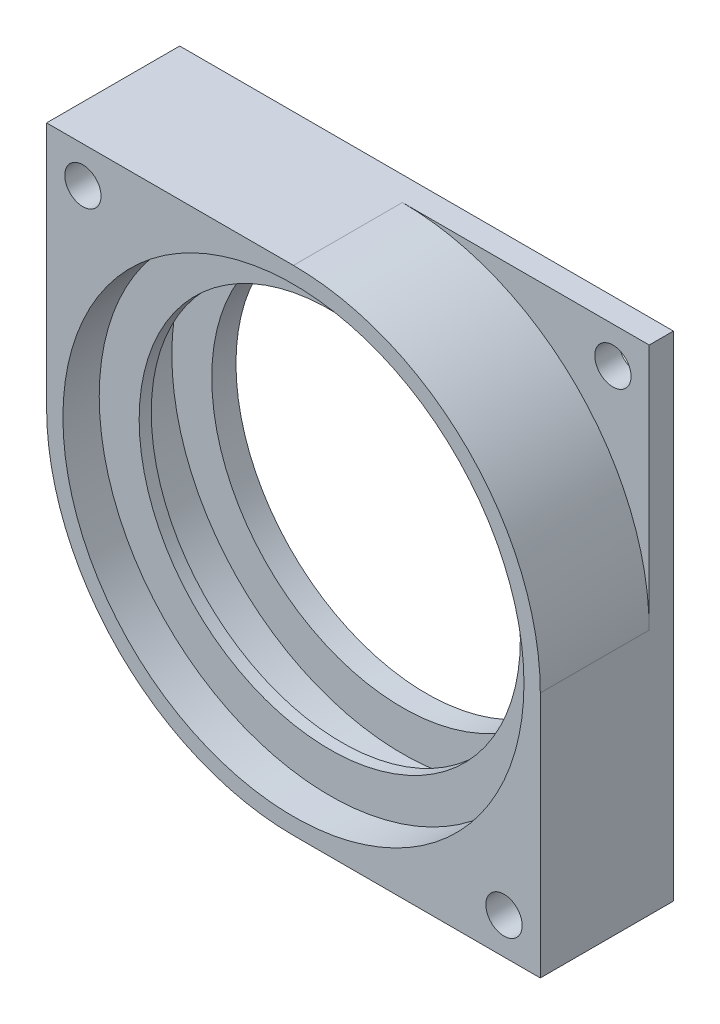
SolidWorks part; units mm, degrees
ref_plane "Front Plane" through (0, 0, 0) normal (0, 0, 1) x (1, 0, 0)
ref_plane "Top Plane" through (0, 0, 0) normal (0, 1, 0) x (1, 0, 0)
ref_plane "Right Plane" through (0, 0, 0) normal (1, 0, 0) x (0, 0, -1)
sketch "Sketch2" plane through (0, 0, 0) normal (0, 0, 1) x (1, 0, 0)
  line L1 (-20.4, -20.4) -> (20.4, -20.4)
  line L2 (-20.4, -20.4) -> (-20.4, 20.4)
  line L3 (-20.4, 20.4) -> (20.4, 20.4)
  line L4 (20.4, -20.4) -> (20.4, 20.4)
  line L5 (-20.4, -20.4) -> (20.4, 20.4) construction
  line L6 (-20.4, 20.4) -> (20.4, -20.4) construction
  circle A0 centre (0, 0) radius 15.75
  circle A1 centre (0, 0) radius 20.4
  circle A2 centre (17.4, 17.4) radius 1.5
  circle A3 centre (17.4, -17.4) radius 1.5
  circle A4 centre (-17.4, -17.4) radius 1.5
  circle A5 centre (-17.4, 17.4) radius 1.5
  point P0 (0, 0)
  point P21 (0, 0)
  dimension "D2" = 31.5
  dimension "D4" = 3
  dimension "D1" = 40.8
  dimension "D3" = 3
  dimension "D5" = 4
extrude "Boss-Extrude1" add sketch "Sketch2" along normal blind 5 contours A1 A0 | A1 L3 L2 A5 | A1 L4 L3 A2 | A1 L1 L4 A3 | A1 L2 L1 A4 region at (-15.7095, -15.7095, 0) region at (15.7095, -15.7095, 0) region at (-14.017, -14.017, 0) region at (-15.7095, 15.7095, 0) region at (15.7095, 15.7095, 0)
extrude "Boss-Extrude2" add sketch "Sketch2<4>" along normal blind 6 from surface contours A1 A0 | A1 L3 L2 A5 | A1 L1 L4 A3 region at (15.7095, -15.7095, 0) region at (-14.017, -14.017, 0) region at (-15.7095, 15.7095, 0) starting at face at (15.75, 0, 5)
sketch "Sketch2<4>" plane through (0, 0, 0) normal (0, 0, 1) x (1, 0, 0) same geometry as "Sketch2"
sketch "Sketch4" plane through (0, 0, 11) normal (0, 0, 1) x (1, 0, 0)
  circle A0 centre (0, 0) radius 15.75 construction
  circle A1 centre (0, 0) radius 15.75
  circle A3 centre (0, 0) radius 19.05
  dimension "D1" = 3.3
extrude "Cut-Extrude2" cut sketch "Sketch4" against normal blind 3 contours A3
sketch "Sketch5" plane through (0, 0, 8) normal (0, 0, 1) x (1, 0, 0)
  circle A0 centre (0, 0) radius 15.75 construction
  circle A1 centre (0, 0) radius 19.05
  circle A2 centre (0, 0) radius 19.05
  circle A3 centre (0, 0) radius 15.75
  dimension "D1" = 0
ref_plane "Plane1" through (0, 0, 2) normal (0, 0, -1) x (-1, 0, 0)
extrude "Cut-Extrude3" cut sketch "Sketch5" along normal offset from surface (5 mm away) 1 from surface up to face at (15.75, 0, 8) starting at plane "Plane1"
sketch "Sketch6" plane through (0, 0, 5) normal (0, 0, 1) x (1, 0, 0)
  line L2 (20.4, 0) -> (20.4, 20.4)
  line L3 (20.4, 20.4) -> (0, 20.4)
  line L4 (20.4, 0) -> (20.4, 20.4)
  line L5 (20.4, 20.4) -> (0, 20.4)
  line L6 (-20.4, 0) -> (-20.4, -20.4)
  line L7 (-20.4, -20.4) -> (0, -20.4)
  line L8 (-20.4, 0) -> (-20.4, -20.4)
  line L9 (-20.4, -20.4) -> (0, -20.4)
  arc A1 (20.4, 0) -> (0, 20.4) centre (0, 0) ccw
  arc A2 (20.4, 0) -> (0, 20.4) centre (0, 0) ccw
  arc A3 (-20.4, 0) -> (0, -20.4) centre (0, 0) ccw
  arc A4 (-20.4, 0) -> (0, -20.4) centre (0, 0) ccw
  dimension "D1" = 0
  dimension "D2" = 0
extrude "Cut-Extrude4" cut sketch "Sketch6" against normal blind 3
